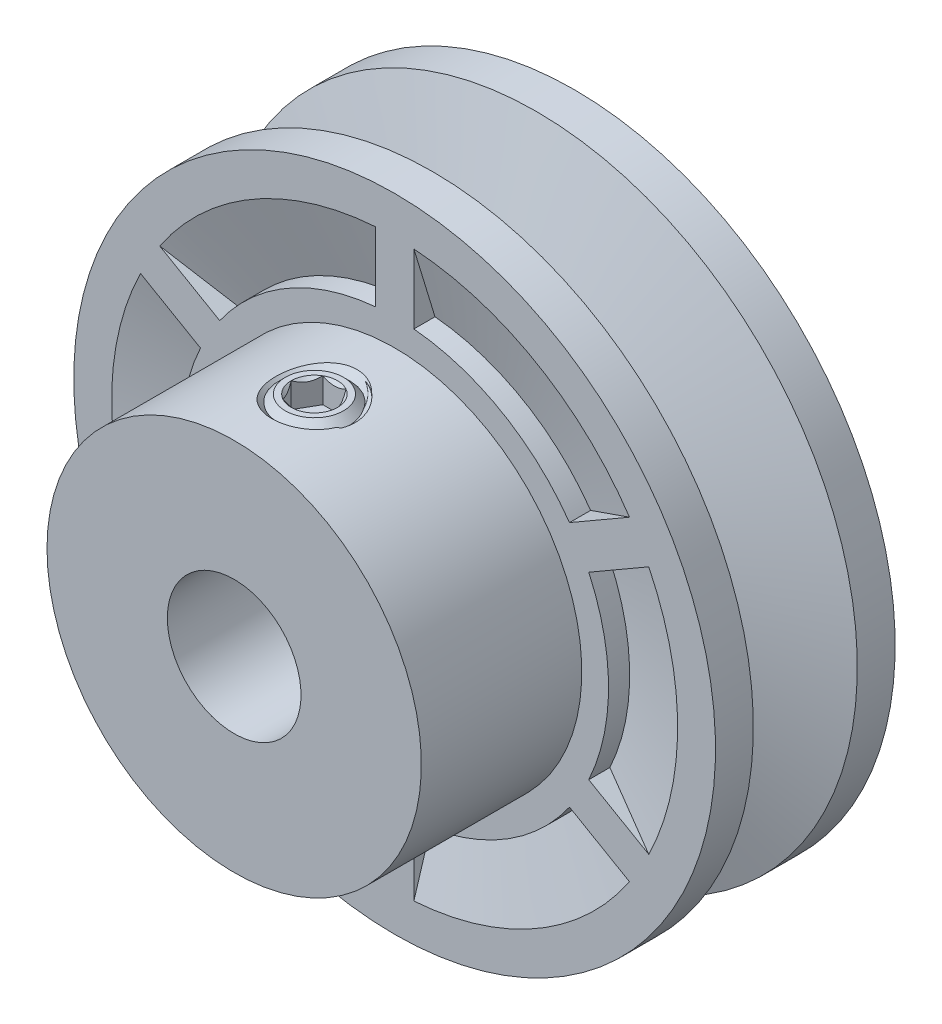
SolidWorks part; units mm, degrees
material "Nylon 101"
ref_plane "Front Plane" through (0, 0, 0) normal (0, 0, 1) x (1, 0, 0)
ref_plane "Top Plane" through (0, 0, 0) normal (0, 1, 0) x (1, 0, 0)
ref_plane "Right Plane" through (0, 0, 0) normal (1, 0, 0) x (0, 0, -1)
sketch "Sketch1" plane through (0, 0, 0) normal (1, 0, 0) x (0, 0, -1)
  line L0 (-14.859, 0) -> (7.366, 0) construction
  line L1 (-3.0861, 19.05) -> (3.0861, 19.05) construction
  line L2 (3.0861, 19.05) -> (5.334, 19.05)
  line L5 (-5.334, 19.05) -> (7.366, 19.05) construction
  line L7 (-5.334, 7.9375) -> (-5.334, 19.05) construction
  line L9 (5.334, 7.9375) -> (-5.334, 7.9375)
  line L10 (-5.334, 16.8021) -> (-1.143, 3.094) construction
  line L12 (7.366, 19.05) -> (7.366, 0) construction
  line L13 (-3.0861, 19.05) -> (-1.1447, 12.7)
  line L14 (-1.1447, 12.7) -> (1.1447, 12.7)
  line L15 (1.1447, 12.7) -> (3.0861, 19.05)
  line L16 (7.366, 3.9687) -> (-14.859, 3.9687) construction
  line L17 (0, 19.05) -> (0, 0) construction
  line L18 (-3.0861, 19.05) -> (-5.334, 19.05)
  line L20 (-14.859, 0) -> (-14.859, 3.9687) construction
  line L22 (5.334, 17.78) -> (-5.334, 17.78) construction
  line L23 (5.334, 12.7) -> (5.334, 19.05) construction
  line L24 (5.334, 16.8021) -> (1.143, 3.094) construction
  line L25 (-1.143, 3.094) -> (-1.143, 12.7) construction
  line L26 (1.143, 3.094) -> (1.143, 12.7) construction
  line L27 (-1.143, 3.094) -> (1.143, 3.094) construction
  line L28 (5.334, 7.9375) -> (5.334, 12.7)
  line L29 (5.334, 12.7) -> (1.143, 12.7) construction
  line L30 (-5.334, 12.7) -> (-5.334, 7.9375)
  line L31 (-1.143, 12.7) -> (-5.334, 12.7) construction
  line L32 (-5.334, 16.8021) -> (-5.334, 19.05)
  line L33 (5.334, 19.05) -> (5.334, 16.8021)
  line L34 (-5.334, 16.8021) -> (-4.0799, 12.7)
  line L35 (-4.0799, 12.7) -> (-5.334, 12.7)
  line L36 (5.334, 16.8021) -> (4.0799, 12.7)
  line L37 (4.0799, 12.7) -> (5.334, 12.7)
  point P16 (0, 12.7)
  point P34 (0, 3.094)
  dimension "D1" = 9.525
  dimension "A" = 34
  dimension "D2" = 15.875
  dimension "OD" = 38.1
  dimension "D3" = 10.668
  dimension "D4" = 2.286
  dimension "D5" = 12.7
  dimension "Bore" = 7.9375
  dimension "Width" = 22.225
  dimension "PD" = 35.56
  dimension "W" = 6.1722
  dimension "Depth" = 6.35
revolve "Revolve1" add sketch "Sketch1" angle 360 about L0
sketch "Sketch2" plane through (0, 0, 0) normal (1, 0, 0) x (0, 0, -1)
  line L0 (-5.334, 16.8021) -> (-2.6238, 7.9375)
  line L1 (-1.143, 3.094) -> (-1.143, 12.7) construction
  line L2 (-2.6238, 7.9375) -> (-5.334, 7.9375)
  line L3 (-5.334, 16.8021) -> (-1.143, 3.094) construction
  line L4 (-1.143, 3.094) -> (-1.143, 7.9375) construction
  line L5 (-1.143, 7.9375) -> (-5.334, 7.9375) construction
  line L6 (-5.334, 16.8021) -> (-1.143, 3.094) construction
  line L7 (-5.334, 16.8021) -> (-5.334, 7.9375)
  line L8 (5.334, 16.8021) -> (2.6238, 7.9375)
  line L9 (2.6238, 7.9375) -> (5.334, 7.9375)
  line L11 (5.334, 7.9375) -> (-5.334, 7.9375) construction
  line L12 (-5.334, 12.7) -> (-5.334, 7.9375) construction
  line L13 (0, 0) -> (0, 19.05) construction
  line L14 (5.334, 16.8021) -> (5.334, 7.9375)
  line L15 (5.334, 16.8021) -> (1.143, 3.094) construction
  line L16 (1.143, 7.9375) -> (5.334, 7.9375) construction
  line L17 (1.143, 3.094) -> (1.143, 7.9375) construction
extrude "Boss-Extrude1" add sketch "Sketch2" along normal mid plane 2.286
pattern_circular "CirPattern1" count 6 over 360 about axis through (0, 0, 14.859) along (0, 0, 1) of "Boss-Extrude1"
sketch "Sketch3" plane through (0, 0, 0) normal (1, 0, 0) x (0, 0, -1)
  line L0 (7.366, 0) -> (-14.859, 0) construction
  line L1 (7.366, 0) -> (7.366, 7.9375)
  line L2 (7.366, 7.9375) -> (-5.334, 7.9375)
  line L3 (-5.334, 7.9375) -> (-5.334, 11.1125)
  line L4 (-5.334, 11.1125) -> (-14.859, 11.1125)
  line L5 (-14.859, 11.1125) -> (-14.859, 0)
  line L6 (5.334, 7.9375) -> (-5.334, 7.9375) construction
  line L7 (-5.334, 12.7) -> (-5.334, 7.9375) construction
  line L8 (-14.859, 0) -> (7.366, 0)
  dimension "D1" = 22.225
revolve "Revolve2" add sketch "Sketch3" angle 360 about L0
sketch "Sketch4" plane through (0, 0, -7.366) normal (0, 0, -1) x (-1, 0, 0)
  circle A0 centre (0, 0) radius 3.9687
  circle A1 centre (0, 0) radius 17.78 construction
extrude "Cut-Extrude1" cut sketch "Sketch4" against normal up to vertex (22.225 mm away) up to point (0, 0, 14.859)
ref_plane "Plane1" through (0, 11.1125, 0) normal (0, 1, 0) x (-1, 0, 0)
sketch "Sketch5" plane through (0, 11.1125, 0) normal (0, 1, 0) x (-1, 0, 0)
  line L0 (0, 5.334) -> (0, 14.859) construction
  line L7 (0, 12.5095) -> (0, 11.4512) construction
  circle A0 centre (0, 10.0965) radius 2.413 construction
  circle A1 centre (0, 10.0965) radius 1.7515
  dimension "D1" = 4.826
  dimension "D2" = 1.0583
  dimension "D3" = 0.6615
extrude "Cut-Extrude2" cut sketch "Sketch5" against normal up to surface (11.1125 mm away) up to plane "Top Plane"
sketch "Sketch6" plane through (0, 11.1125, 0) normal (0, 1, 0) x (-1, 0, 0)
  circle A0 centre (0, 10.0965) radius 2.413 construction
  circle A1 centre (0, 10.0965) radius 2.413
  point P3 (0, 12.5095)
curve "Helix/Spiral1" pitch 1.0583 height 12.1708 radius 2.413 centre (0, 11.1125, 10.0965) axis (0, -1, 0) start towards (0, 0, 1)
sketch "Sketch7" plane through (0, 0, 0) normal (1, 0, 0) x (0, 0, -1)
  line L0 (-11.7075, 12.1708) -> (-11.7075, 11.1125) construction
  line L1 (-11.7075, 11.1125) -> (-12.6241, 11.6417) construction
  line L2 (-12.6241, 11.6417) -> (-11.7075, 12.1708) construction
  line L3 (-11.7075, 11.1125) -> (-12.5095, 11.1125) construction
  line L4 (-12.5095, 11.1125) -> (-12.5095, 11.5755) construction
  line L5 (-12.5095, 11.5755) -> (-12.5095, 11.7078) construction
  line L6 (-11.8221, 11.1786) -> (-11.8221, 12.1047) construction
  line L7 (-12.6241, 11.6417) -> (-12.5095, 11.6417) construction
  line L8 (-11.8221, 11.6417) -> (-11.7075, 11.6417) construction
  line L9 (-11.7648, 12.1378) -> (-11.7648, 11.1456)
  line L10 (-11.7648, 11.1456) -> (-12.5095, 11.5755)
  line L11 (-12.5095, 11.5755) -> (-12.5095, 11.7078)
  line L12 (-12.5095, 11.7078) -> (-11.7648, 12.1378)
  point P16 (-11.7648, 11.6417)
  dimension "D1" = 1.0583
  dimension "D2" = 0.1323
sweep "Cut-Sweep1" cut profiles "Sketch7" path "Helix/Spiral1" align with end faces yes
sketch "Sketch8" plane through (0, 11.1125, 0) normal (0, 1, 0) x (-1, 0, 0)
  circle A0 centre (0, 10.0965) radius 2.5276
extrude "Cut-Extrude3" cut sketch "Sketch8" against normal through all draft 45
sketch "Sketch9" plane through (0, 0, 0) normal (1, 0, 0) x (0, 0, -1)
  line L0 (-10.0965, 11.1125) -> (-10.0965, 4.7625) construction
  line L1 (-12.5095, 5.4499) -> (-12.5095, 10.4251)
  line L2 (-10.0965, 11.1125) -> (-12.5095, 11.1125) construction
  line L3 (-10.0965, 11.1125) -> (-10.0965, 4.7625)
  line L4 (-10.0965, 4.7625) -> (-12.5095, 4.7625) construction
  line L5 (-12.5095, 11.1125) -> (-12.5095, 4.7625) construction
  line L6 (-11.8221, 11.1125) -> (-12.5095, 10.4251)
  line L7 (-12.5095, 5.4499) -> (-11.8221, 4.7625)
  line L8 (-11.8221, 11.1125) -> (-10.0965, 11.1125)
  line L9 (-11.8221, 4.7625) -> (-10.0965, 4.7625)
  line L10 (-5.334, 11.1125) -> (-14.859, 11.1125) construction
  line L11 (-11.8221, 11.1125) -> (-12.5095, 11.1125) construction
  line L12 (-12.5095, 11.1125) -> (-12.5095, 10.4251) construction
  line L13 (-11.8221, 11.1786) -> (-11.8221, 12.1047) construction
  dimension "D1" = 6.35
revolve "Revolve3" add sketch "Sketch9" angle 360 about L0
sketch "Sketch10" plane through (0, 11.1125, 0) normal (0, 1, 0) x (1, 0, 0)
  line L1 (1.3748, -10.0965) -> (0.6874, -8.9059)
  line L2 (0.6874, -8.9059) -> (-0.6874, -8.9059)
  line L3 (-0.6874, -8.9059) -> (-1.3748, -10.0965)
  line L4 (-1.3748, -10.0965) -> (-0.6874, -11.2871)
  line L5 (-0.6874, -11.2871) -> (0.6874, -11.2871)
  line L6 (0.6874, -11.2871) -> (1.3748, -10.0965)
  circle A0 centre (0, -10.0965) radius 1.1906 construction
  dimension "D1" = 2.3813
extrude "Cut-Extrude4" cut sketch "Sketch10" against normal blind 1.4883
sketch "Sketch11" plane through (0, 11.1125, 0) normal (0, 1, 0) x (1, 0, 0)
  circle A0 centre (0, -10.0965) radius 1.3748
extrude "Cut-Extrude5" cut sketch "Sketch11" against normal through all draft 45
equation "\"D3@Sketch5\" = \"D2@Sketch5\" * 5 / 8"
equation "\"D4@Helix/Spiral1\" = \"D2@Sketch5\""
equation "\"D3@Helix/Spiral1\" = \"D4@Helix/Spiral1\" + ( \"D1@Sketch3\" / 2 ) "
equation "\"D1@Sketch7\" = \"D4@Helix/Spiral1\""
equation "\"D2@Sketch7\" = \"D1@Sketch7\" / 8"
